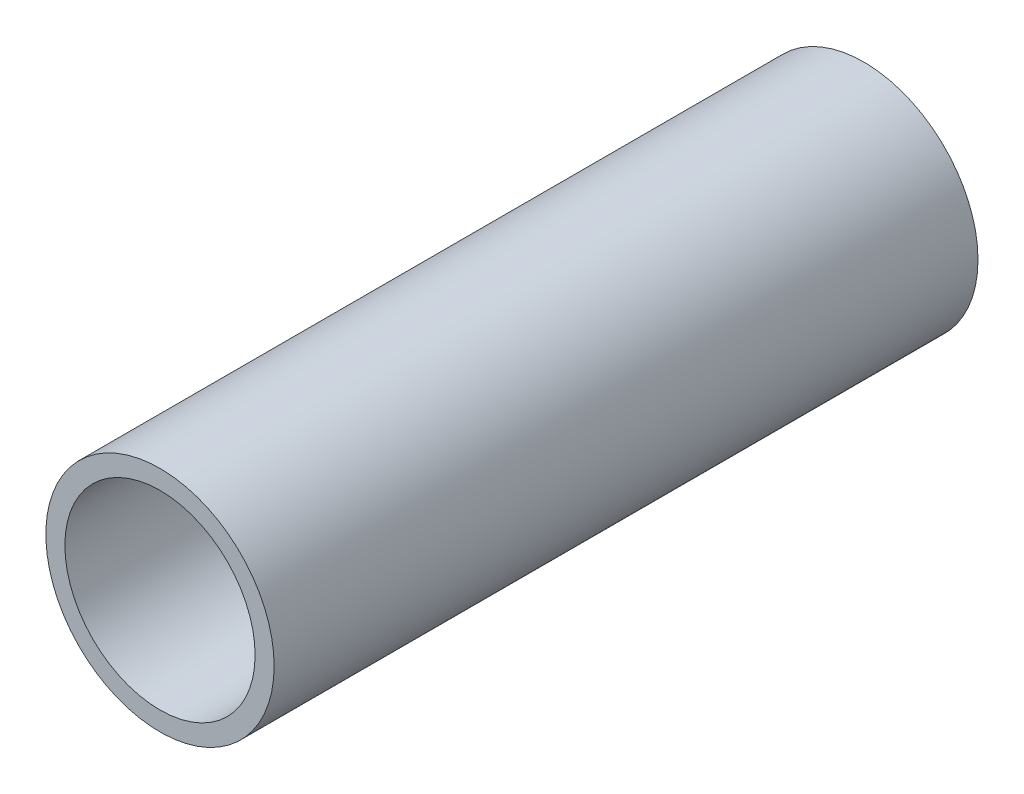
SolidWorks part; units mm, degrees
material "1023 Tôle d'acier au carbone (SS)"
ref_plane "Plan de face" through (0, 0, 0) normal (0, 0, 1) x (1, 0, 0)
ref_plane "Plan de dessus" through (0, 0, 0) normal (0, 1, 0) x (1, 0, 0)
ref_plane "Plan de droite" through (0, 0, 0) normal (1, 0, 0) x (0, 0, -1)
sketch "Esquisse1" plane through (0, 0, 0) normal (0, 0, 1) x (1, 0, 0)
  circle A0 centre (0, 0) radius 6
  circle A1 centre (0, 0) radius 5
  dimension "D1" = 12
  dimension "D2" = 1
extrude "Boss.-Extru.1" add sketch "Esquisse1" along normal blind 37
